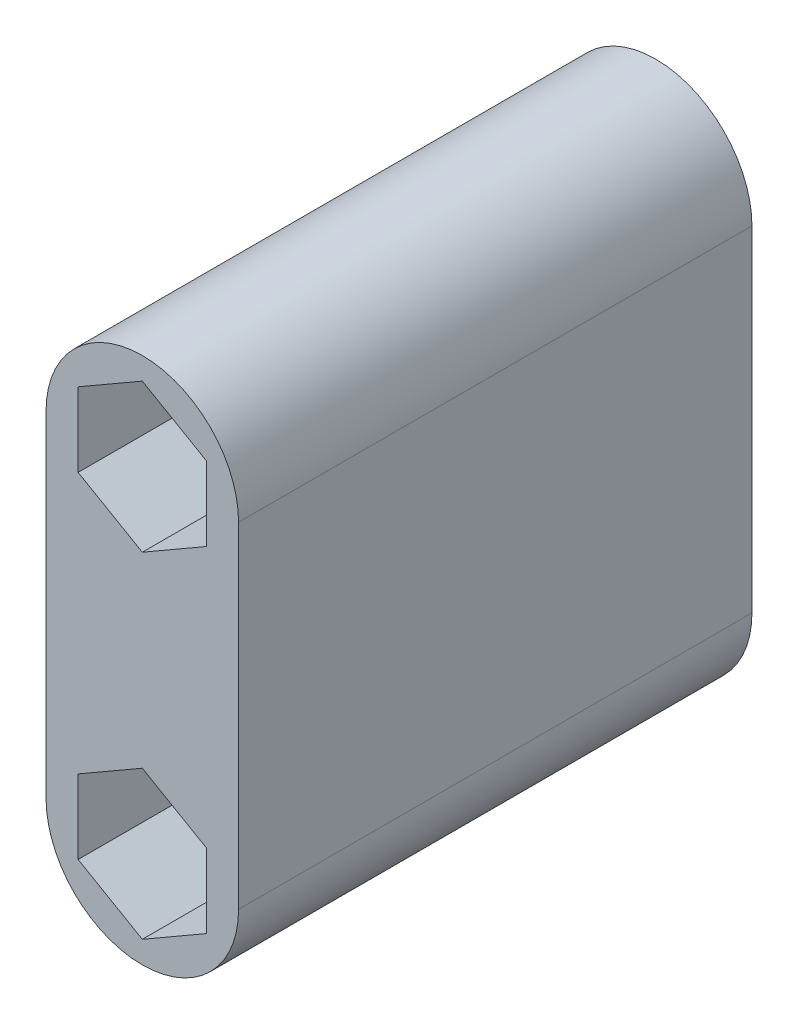
SolidWorks part; units mm, degrees
ref_plane "Front Plane" through (0, 0, 0) normal (0, 0, 1) x (1, 0, 0)
ref_plane "Top Plane" through (0, 0, 0) normal (0, 1, 0) x (1, 0, 0)
ref_plane "Right Plane" through (0, 0, 0) normal (1, 0, 0) x (0, 0, -1)
sketch "Sketch1" plane through (0, 0, 0) normal (0, 0, 1) x (1, 0, 0)
  line L0 (0, 0) -> (0, 16.5862) construction
  line L1 (-4.7625, 0) -> (-4.7625, 16.5862)
  line L2 (4.7625, 0) -> (4.7625, 16.5862)
  arc A0 (-4.7625, 0) -> (4.7625, 0) centre (0, 0) ccw
  arc A1 (4.7625, 16.5862) -> (-4.7625, 16.5862) centre (0, 16.5862) ccw
  point P3 (0, 8.2931)
  dimension "D1" = 4.7625
  dimension "D2" = 16.5862
extrude "Boss-Extrude1" add sketch "Sketch1" along normal blind 25.4
sketch "Sketch2" plane through (0, 0, 25.4) normal (0, 0, 1) x (1, 0, 0)
  line L1 (0, 20.2524) -> (-3.175, 18.4193)
  line L2 (-3.175, 18.4193) -> (-3.175, 14.7531)
  line L3 (-3.175, 14.7531) -> (0, 12.92)
  line L4 (0, 12.92) -> (3.175, 14.7531)
  line L5 (3.175, 14.7531) -> (3.175, 18.4193)
  line L6 (3.175, 18.4193) -> (0, 20.2524)
  line L7 (0, 3.6662) -> (-3.175, 1.8331)
  line L8 (-3.175, 1.8331) -> (-3.175, -1.8331)
  line L9 (-3.175, -1.8331) -> (0, -3.6662)
  line L10 (0, -3.6662) -> (3.175, -1.8331)
  line L11 (3.175, -1.8331) -> (3.175, 1.8331)
  line L12 (3.175, 1.8331) -> (0, 3.6662)
  circle A2 centre (0, 16.5862) radius 3.175 construction
  circle A3 centre (0, 0) radius 3.175 construction
  dimension "D1" = 6.35
extrude "Cut-Extrude1" cut sketch "Sketch2" against normal through all
sketch "Sketch3" [suppressed] plane through (0, 0, 25.4) normal (0, 0, 1) x (1, 0, 0)
  line L0 (3.2365, 20.08) -> (8.4769, 15.2254)
  line L1 (8.7312, 14.6431) -> (8.7312, 1.9431)
  line L2 (8.4769, 1.3608) -> (3.2365, -3.4938)
  line L3 (4.7625, 0) -> (4.7625, 16.5862) construction
  line L4 (4.7625, 0) -> (4.7625, 16.5862)
  arc A0 (4.7625, 16.5862) -> (-4.7625, 16.5862) centre (0, 16.5862) ccw construction
  arc A1 (8.4769, 15.2254) -> (8.7312, 14.6431) centre (7.9375, 14.6431) cw
  arc A2 (8.7312, 1.9431) -> (8.4769, 1.3608) centre (7.9375, 1.9431) cw
  arc A3 (-4.7625, 0) -> (4.7625, 0) centre (0, 0) ccw construction
  arc A4 (3.2365, -3.4938) -> (4.7625, 0) centre (0, 0) ccw
  arc A5 (4.7625, 16.5862) -> (3.2365, 20.08) centre (0, 16.5862) ccw
  point P16 (4.7625, 8.2931)
  point P17 (8.7312, 8.2931)
  dimension "D3" = 0.7937
  dimension "D1" = 3.9688
  dimension "D2" = 12.7
extrude "Boss-Extrude2" [suppressed] add sketch "Sketch3" against normal up to surface (25.4 mm away) up to face at (0, 16.5862, 0)
sketch "Sketch4" [suppressed] plane through (0, 0, 14.2875) normal (0, 0, 1) x (1, 0, 0)
  circle A0 centre (0, 16.5862) radius 2.159
  circle A1 centre (0, 0) radius 2.159
  dimension "D1" = 4.318
extrude "Cut-Extrude2" [suppressed] cut sketch "Sketch4" against normal through all
